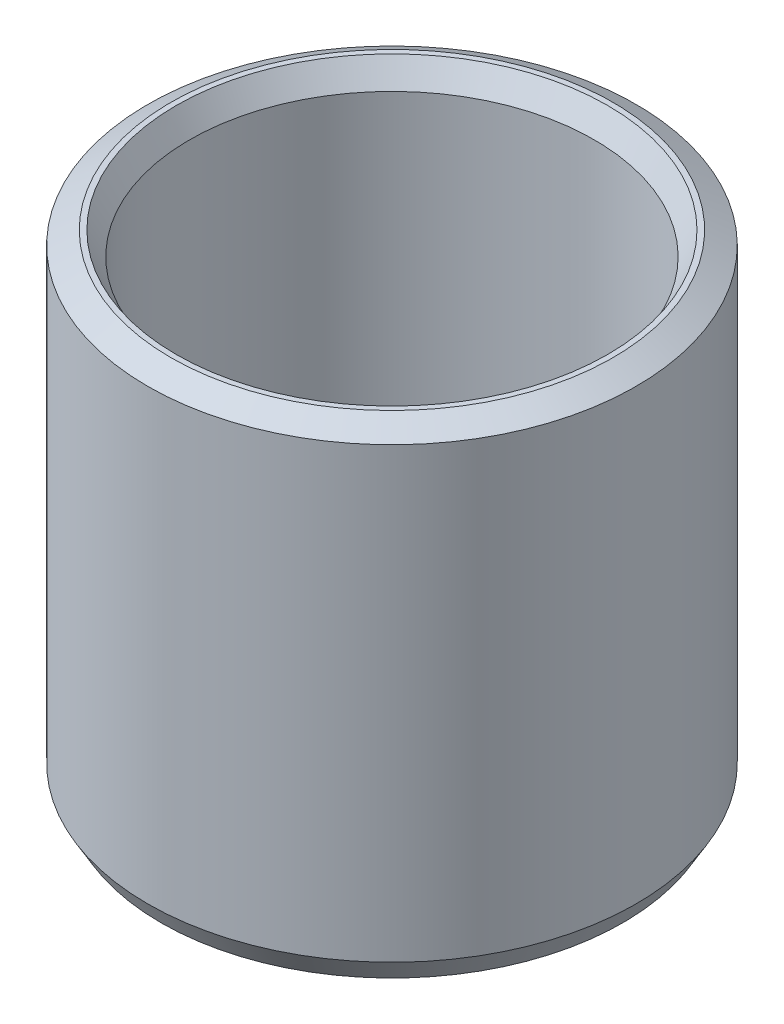
SolidWorks part; units mm, degrees
ref_plane "Front Plane" through (0, 0, 0) normal (0, 0, 1) x (1, 0, 0)
ref_plane "Top Plane" through (0, 0, 0) normal (0, 1, 0) x (1, 0, 0)
ref_plane "Right Plane" through (0, 0, 0) normal (1, 0, 0) x (0, 0, -1)
sketch "Sketch1" plane through (0, 0, 0) normal (0, 1, 0) x (1, 0, 0)
  circle A0 centre (0, 0) radius 32.5
  dimension "SLEEVE_OD" = 65
extrude "Boss-Extrude1" add sketch "Sketch1" along normal blind 64.4995
sketch "Sketch2" plane through (0, 0, 0) normal (0, 1, 0) x (1, 0, 0)
  circle A0 centre (0, 0) radius 26.9363
  dimension "BORE_D" = 53.8727
extrude "Cut-Extrude1" cut sketch "Sketch2" along normal through all
chamfer "Chamfer1" distance 1.7736 angle 60 4 edges at (0, 64.4995, 26.9363) (0, 0, 26.9363) (0, 0, 32.5) (0, 64.4995, 32.5) first distance on face at (0, 64.4995, 26.9363) first distance on face at (0, 0, 26.9363) first distance on face at (0, 64.4995, 32.5)
